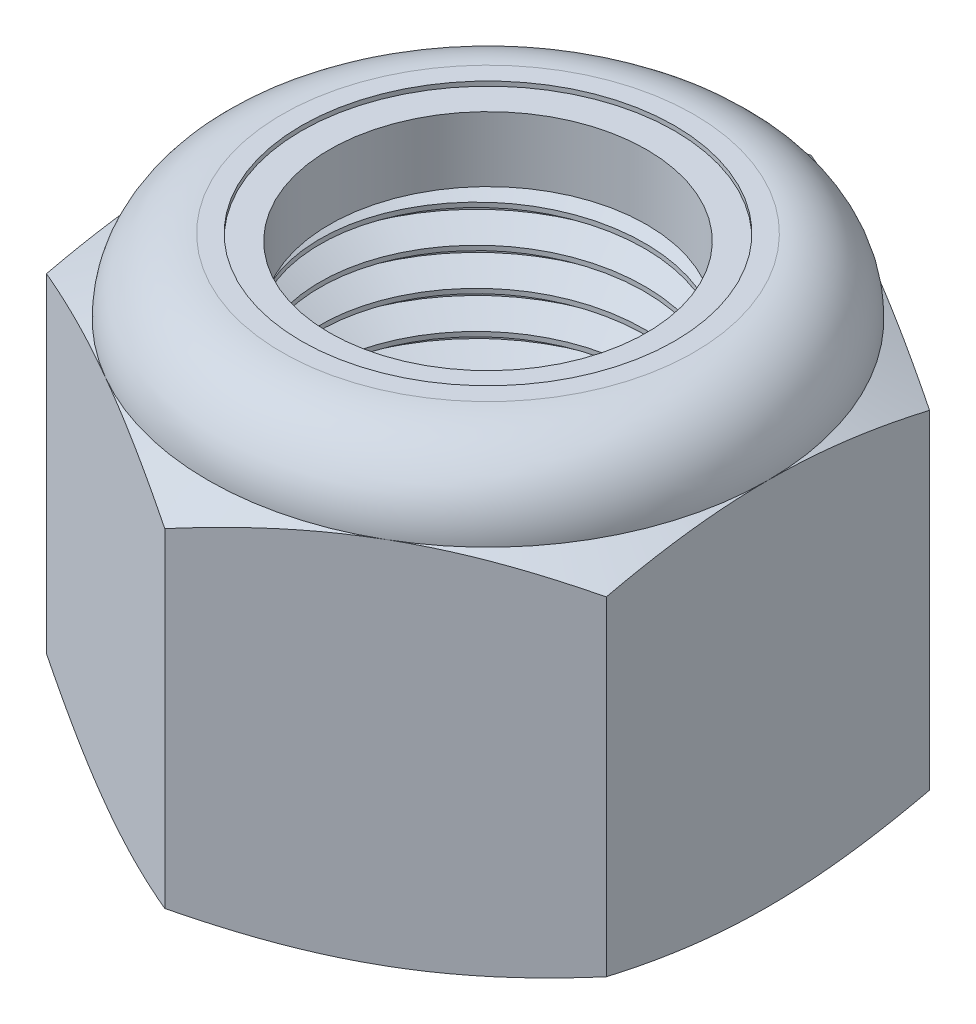
SolidWorks part; units mm, degrees
ref_plane "Front" through (0, 0, 0) normal (0, 0, 1) x (1, 0, 0)
ref_plane "Top" through (0, 0, 0) normal (0, 1, 0) x (1, 0, 0)
ref_plane "Right" through (0, 0, 0) normal (1, 0, 0) x (0, 0, -1)
sketch "Sketch1" plane through (0, 0, 0) normal (1, 0, 0) x (0, 0, -1)
  line L0 (0, 0) -> (0, 15.0812) construction
  line L1 (9.525, 0) -> (-9.525, 0) construction
  line L2 (-6.35, 15.0812) -> (6.35, 15.0812) construction
  line L3 (6.35, 15.0812) -> (6.35, 13.8112) construction
  point P9 (-6.35, 15.0812)
  point P10 (6.35, 15.0812)
  point P11 (9.525, 0)
  dimension "Height" = 15.0812
  dimension "Hex Flats" = 19.05
  dimension "Thread Dia" = 12.7
  dimension "Thread Pitch" = 1.27
sketch "Sketch13" plane through (0, 0, 0) normal (0, 1, 0) x (1, 0, 0)
  line L1 (0, 10.9985) -> (-9.525, 5.4993)
  line L2 (-9.525, 5.4993) -> (-9.525, -5.4993)
  line L3 (-9.525, -5.4993) -> (0, -10.9985)
  line L4 (0, -10.9985) -> (9.525, -5.4993)
  line L5 (9.525, -5.4993) -> (9.525, 5.4993)
  line L6 (9.525, 5.4993) -> (0, 10.9985)
  circle A0 centre (0, 0) radius 9.525 construction
  circle A1 centre (0, 0) radius 6.35
  point P11 (0, -6.35)
  point P13 (0, 6.35)
extrude "Extrude1" add sketch "Sketch13" along normal up to vertex (15.0813 mm away) up to point (0, 15.0812, 0)
sketch "Sketch5" plane through (0, 0, 0) normal (1, 0, 0) x (0, 0, -1)
  line L0 (0, 0) -> (9.525, 0)
  line L1 (9.525, 0) -> (10.9985, 0.6871)
  line L2 (10.9985, 0.6871) -> (10.9985, 11.8806)
  line L3 (10.9985, 11.8806) -> (9.525, 12.5677)
  line L4 (7.0115, 15.0812) -> (7.0115, 16.3512)
  line L5 (7.0115, 16.3512) -> (12.2685, 16.3512)
  line L6 (12.2685, 16.3512) -> (12.2685, -1.27)
  line L7 (12.2685, -1.27) -> (0, -1.27)
  line L8 (0, -1.27) -> (0, 0)
  line L9 (9.525, 12.5677) -> (9.525, 0) construction
  line L12 (10.9985, 15.0812) -> (10.9985, 0) construction
  line L13 (10.9985, 7.5406) -> (12.2685, 7.5406) construction
  line L15 (0, 0) -> (0, 16.3512) construction
  line L18 (9.525, 0) -> (-9.525, 0) construction
  line L19 (5.4993, 15.0812) -> (10.9985, 15.0812) construction
  line L20 (0, 16.3512) -> (7.0115, 16.3512) construction
  line L21 (5.4993, 0) -> (10.9985, 0) construction
  arc A0 (9.525, 12.5677) -> (7.0115, 15.0812) centre (7.0115, 12.5677) ccw
  dimension "D1" = 25
  dimension "D2" = 1.27
  dimension "D4" = 2.5135
revolve "Cut-Revolve3" cut sketch "Sketch5" angle 360 about L15
sketch "Sketch4" plane through (0, 0, 0) normal (1, 0, 0) x (0, 0, -1)
  line L0 (0, 12.5677) -> (6.985, 12.5677)
  line L1 (6.985, 12.5677) -> (0, 9.3105)
  line L3 (0, 3.2572) -> (6.985, 0)
  line L4 (6.985, 0) -> (0, 0)
  line L5 (0, 0) -> (0, 12.5677) construction
  line L10 (0, 0) -> (0, 15.0812) construction
  line L11 (0, 3.2572) -> (0, 0)
  line L12 (0, 12.5677) -> (0, 9.3105)
  line L13 (8.2489, 12.5677) -> (0, 12.5677) construction
  dimension "D1" = 25
  dimension "D2" = 13.97
sketch "Sketch6" plane through (0, 0, 0) normal (1, 0, 0) x (0, 0, -1)
  line L0 (0, 12.5677) -> (9.3726, 12.5677)
  line L1 (7.0115, 14.9289) -> (3.5057, 14.9289)
  line L2 (0, 16.3512) -> (0, 12.5677)
  line L3 (3.5057, 16.3512) -> (0, 16.3512)
  line L4 (0, 16.3512) -> (7.0115, 16.3512) construction
  line L5 (0, 0) -> (0, 16.3512) construction
  line L6 (0, 16.3512) -> (0, 0) construction
  line L7 (3.5057, 14.9289) -> (3.5057, 16.3512)
  line L8 (7.0115, 15.0812) -> (7.0115, 14.9289) construction
  line L9 (3.5057, 14.9289) -> (0, 14.9289) construction
  line L10 (0, 14.9289) -> (0, 9.3105) construction
  arc A0 (9.3726, 12.5677) -> (7.0115, 14.9289) centre (7.0115, 12.5677) ccw
  arc A1 (9.525, 12.5677) -> (7.0115, 15.0812) centre (7.0115, 12.5677) ccw construction
  dimension "D1" = 0.1524
revolve "Cut-Revolve4" cut sketch "Sketch6" angle 360 about L6
revolve "Cut-Revolve2" cut sketch "Sketch4" angle 360 about L5
sketch "Sketch7" plane through (0, 0, 0) normal (1, 0, 0) x (0, 0, -1)
  line L0 (5.3975, 12.6439) -> (9.2951, 12.6439)
  line L1 (7.0115, 14.8527) -> (5.3975, 14.8527)
  line L2 (5.3975, 14.8527) -> (5.3975, 12.6439)
  line L3 (5.3975, 12.6439) -> (0, 12.6439) construction
  line L4 (0, 12.6439) -> (0, 14.8527) construction
  line L5 (0, 14.8527) -> (5.3975, 14.8527) construction
  line L6 (5.3975, 12.6439) -> (5.3975, 12.5677) construction
  line L7 (0, 12.5677) -> (9.3726, 12.5677) construction
  line L8 (7.0115, 14.8527) -> (7.0115, 14.9289) construction
  arc A0 (9.2951, 12.6439) -> (7.0115, 14.8527) centre (7.0115, 12.5677) ccw
  arc A2 (9.3726, 12.5677) -> (7.0115, 14.9289) centre (7.0115, 12.5677) ccw construction
  point P15 (5.3975, 14.8527)
  point P18 (-6.2045, 14.8527)
  point P19 (6.2045, 14.8527)
  dimension "D1" = 0.0762
  dimension "D2" = 10.795
revolve "Revolve2" add sketch "Sketch7" angle 360 about L4
sketch "Sketch2" plane through (0, 0, 0) normal (1, 0, 0) x (0, 0, -1)
  line L0 (-6.35, 0) -> (-6.35, 12.5677) construction
  line L1 (0, 0) -> (6.35, 0)
  line L2 (0, 0) -> (0, 12.5677)
  line L3 (0, 12.5677) -> (6.35, 12.5677)
  line L4 (6.35, 0) -> (6.35, 12.5677)
  line L6 (8.2489, 12.5677) -> (9.525, 12.5677) construction
  line L7 (0, -6.35) -> (0, 0) construction
revolve "Revolve1" add sketch "Sketch2" angle 360 about L7
sketch "Sketch9" plane through (0, 0, 0) normal (1, 0, 0) x (0, 0, -1)
  line L0 (6.4875, 13.7583) -> (6.4875, 12.4883) construction
  line L1 (6.4875, 12.4883) -> (5.3876, 13.1233) construction
  line L2 (5.3876, 13.1233) -> (6.4875, 13.7583) construction
  line L3 (5.5251, 13.2027) -> (5.5251, 13.044) construction
  line L4 (6.35, 13.679) -> (6.35, 12.5677) construction
  line L5 (5.3876, 13.1233) -> (5.5251, 13.1233) construction
  line L6 (6.35, 13.1233) -> (6.4875, 13.1233) construction
  line L7 (6.4187, 13.1233) -> (6.4187, 13.7186) construction
  line L8 (6.4875, 12.4883) -> (6.4187, 13.7186)
  line L9 (6.4187, 13.7186) -> (5.5251, 13.2027)
  line L10 (5.5251, 13.2027) -> (5.5251, 13.044)
  line L11 (5.5251, 13.044) -> (6.4875, 12.4883)
  dimension "D1" = 1.27
  dimension "D2" = 0.1588
sketch "Sketch10" plane through (0, 12.5677, 0) normal (0, 1, 0) x (1, 0, 0)
  circle A1 centre (0, 0) radius 6.35
  circle A2 centre (0, 0) radius 6.35
  dimension "D1" = 0
curve "Helix/Spiral1" pitch 1.27 height 16.3513 turns 12.875
sweep "Cut-Sweep1" cut profiles "Sketch9" path "Helix/Spiral1"
sketch "Sketch11" plane through (0, 0, 0) normal (1, 0, 0) x (0, 0, -1)
  line L0 (0, 0) -> (0, 15.0812) construction
  line L1 (9.525, 0) -> (-9.525, 0) construction
  line L4 (0, 15.0812) -> (0, 0) construction
  line L5 (0, 7.5406) -> (6.35, 7.5406) construction
  line L6 (0, 0) -> (6.985, 0)
  line L7 (0, 3.2572) -> (0, 0)
  line L8 (6.985, 0) -> (0, 3.2572)
  dimension "D1" = 13.97
  dimension "D2" = 25
revolve "Revolve3" add sketch "Sketch11" angle 360 about L4
sketch "Sketch12" plane through (0, 0, 0) normal (1, 0, 0) x (0, 0, -1)
  line L0 (6.985, 12.5677) -> (0, 12.5677)
  line L1 (0, 12.5677) -> (0, 0)
  line L2 (0, 0) -> (6.985, 0)
  line L3 (9.525, 0) -> (-9.525, 0) construction
  line L4 (6.985, 0) -> (6.985, 12.5677)
  line L5 (-6.985, 0) -> (6.985, 0) construction
revolve "Revolve4" add sketch "Sketch12" angle 360 about L0
combine bodies "Combine1" bodies to combine 136 133
equation "\"D4@Sketch5\" = \"Height@Sketch1\" / 6"
equation "\"D1@Sketch9\" = \"Thread Pitch@Sketch1\""
equation "\"D2@Sketch9\" = \"Thread Pitch@Sketch1\" / 8"
equation "\"D4@Helix/Spiral1\" = \"Thread Pitch@Sketch1\""
equation "\"D3@Helix/Spiral1\" = \"Thread Pitch@Sketch1\" + \"Height@Sketch1\""
equation "\"D2@Sketch4\" = \"Thread Dia@Sketch1\" * 1.1"
equation "\"D1@Sketch11\" = \"Thread Dia@Sketch1\" * 1.1"
equation "\"D2@Sketch7\" = \"Thread Dia@Sketch1\" * .85"
